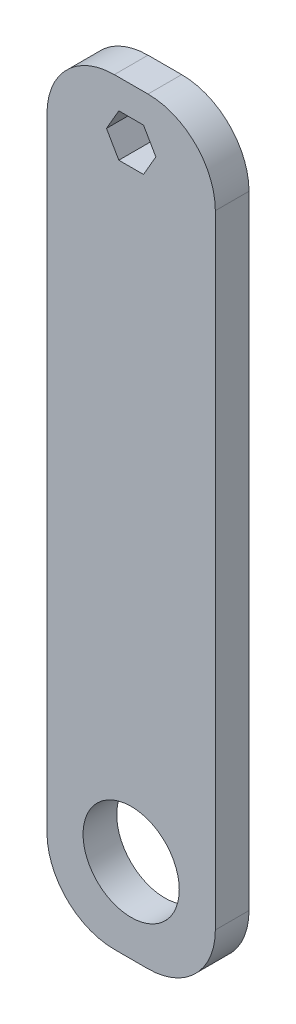
SolidWorks part; units mm, degrees
ref_plane "Front Plane" through (0, 0, 0) normal (0, 0, 1) x (1, 0, 0)
ref_plane "Top Plane" through (0, 0, 0) normal (0, 1, 0) x (1, 0, 0)
ref_plane "Right Plane" through (0, 0, 0) normal (1, 0, 0) x (0, 0, -1)
sketch "Sketch1" plane through (0, 0, 0) normal (0, 1, 0) x (1, 0, 0)
  line L1 (-25, -5) -> (25, -5)
  line L2 (-25, -5) -> (-25, 5)
  line L3 (-25, 5) -> (25, 5)
  line L4 (25, -5) -> (25, 5)
  line L5 (-25, -5) -> (25, 5) construction
  line L6 (-25, 5) -> (25, -5) construction
  point P0 (0, 0)
  dimension "D1" = 50
  dimension "D2" = 10
extrude "Boss-Extrude1" add sketch "Sketch1" along normal mid plane 225
ref_plane "Plane1" through (0, 97.5, 0) normal (0, 1, 0) x (1, 0, 0)
sketch "Sketch2" plane through (0, 0, 5) normal (0, 0, 1) x (1, 0, 0)
  line L0 (0, -5.5) -> (0, 5.5) construction
  line L1 (5.5, 97.5) -> (-5.5, 97.5) construction
  line L2 (3.6662, 91.15) -> (7.3323, 97.5)
  line L3 (7.3323, 97.5) -> (3.6662, 103.85)
  line L4 (3.6662, 103.85) -> (-3.6662, 103.85)
  line L5 (-3.6662, 103.85) -> (-7.3323, 97.5)
  line L6 (-7.3323, 97.5) -> (-3.6662, 91.15)
  line L8 (-25, -112.5) -> (25, -112.5) construction
  line L9 (-3.6662, 91.15) -> (3.6662, 91.15)
  circle A0 centre (0, 97.5) radius 6.35 construction
  circle A2 centre (0, -87.5) radius 14.2875
  point P14 (0, -87.5)
  dimension "D1" = 12.7
  dimension "D2" = 25
  dimension "D3" = 28.575
extrude "Cut-Extrude1" cut sketch "Sketch2" against normal blind 127
fillet "Fillet1" radius 20 4 edges at (-25, -112.5, 0) (25, -112.5, 0) (25, 112.5, 0) (-25, 112.5, 0)
ref_axis "Axis1" [suppressed] through (0, -87.5, -5) along (0, 0, 1)
ref_axis "Axis2" through (0, 97.5, -5.5) along (0, 0, 1)
